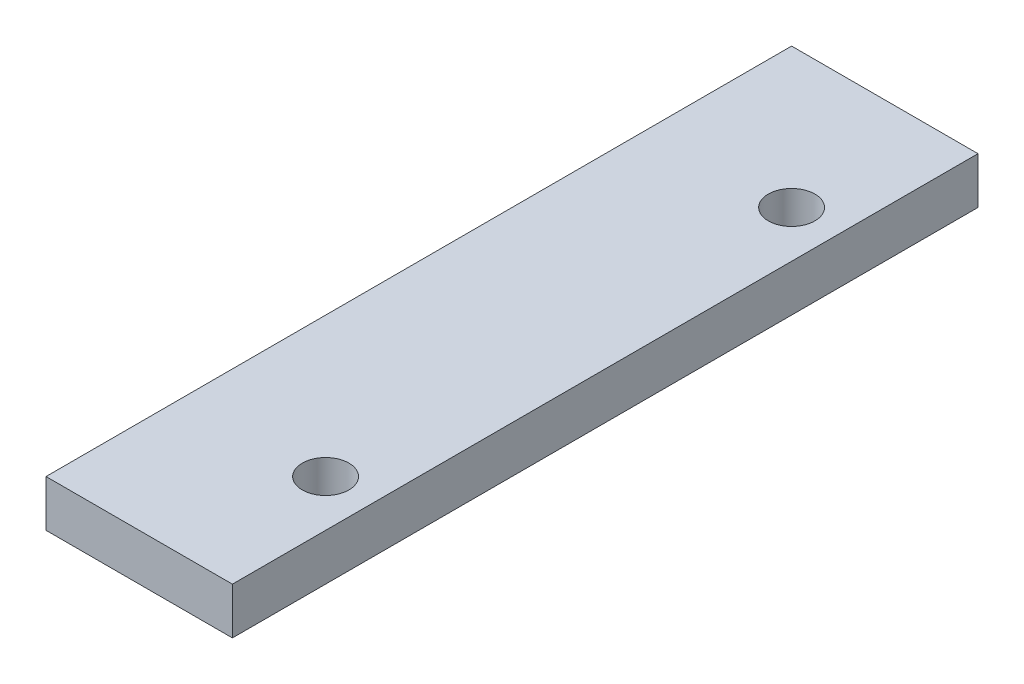
SolidWorks part; units mm, degrees
ref_plane "Front Plane" through (0, 0, 0) normal (0, 0, 1) x (1, 0, 0)
ref_plane "Top Plane" through (0, 0, 0) normal (0, 1, 0) x (1, 0, 0)
ref_plane "Right Plane" through (0, 0, 0) normal (1, 0, 0) x (0, 0, -1)
sketch "Sketch1" plane through (0, 0, 0) normal (0, 1, 0) x (1, 0, 0)
  line L1 (12.7, -50.8) -> (-12.7, -50.8)
  line L2 (12.7, -50.8) -> (12.7, 50.8)
  line L3 (12.7, 50.8) -> (-12.7, 50.8)
  line L4 (-12.7, -50.8) -> (-12.7, 50.8)
  line L5 (12.7, -50.8) -> (-12.7, 50.8) construction
  line L6 (12.7, 50.8) -> (-12.7, -50.8) construction
  point P0 (0, 0)
  dimension "D1" = 101.6
  dimension "D2" = 25.4
extrude "Boss-Extrude1" add sketch "Sketch1" along normal mid plane 6.35
hole_wizard "1/4 (0.25) Diameter Hole1" positions "Sketch2" profile "Sketch3" hole size "1/4" standard "ANSI Inch" end condition through all
sketch "Sketch2" plane through (0, 3.175, 0) normal (0, 1, 0) x (1, 0, 0)
  line L0 (-12.7, -50.8) -> (12.7, -50.8) construction
  line L1 (12.7, 50.8) -> (-12.7, 50.8) construction
  line L2 (12.7, -50.8) -> (12.7, 50.8) construction
  point P0 (6.35, -31.75)
  point P2 (6.35, 31.75)
  dimension "D1" = 19.05
  dimension "D2" = 19.05
  dimension "D3" = 6.35
  dimension "D4" = 6.35
sketch "Sketch3" plane through (6.35, 3.175, 31.75) normal (1, 0, 0) x (0, 0, 1)
  line L0 (0, 0) -> (0, 6.35)
  line L1 (0, 6.35) -> (3.175, 6.35)
  line L2 (3.175, 6.35) -> (3.175, 0)
  line L5 (3.175, 0) -> (0, 0)
  line L11 (0, -6.35) -> (0, 107.95) construction
  dimension "Thru Hole Dia." = 6.35
  dimension "Thru Hole Depth" = 6.35
